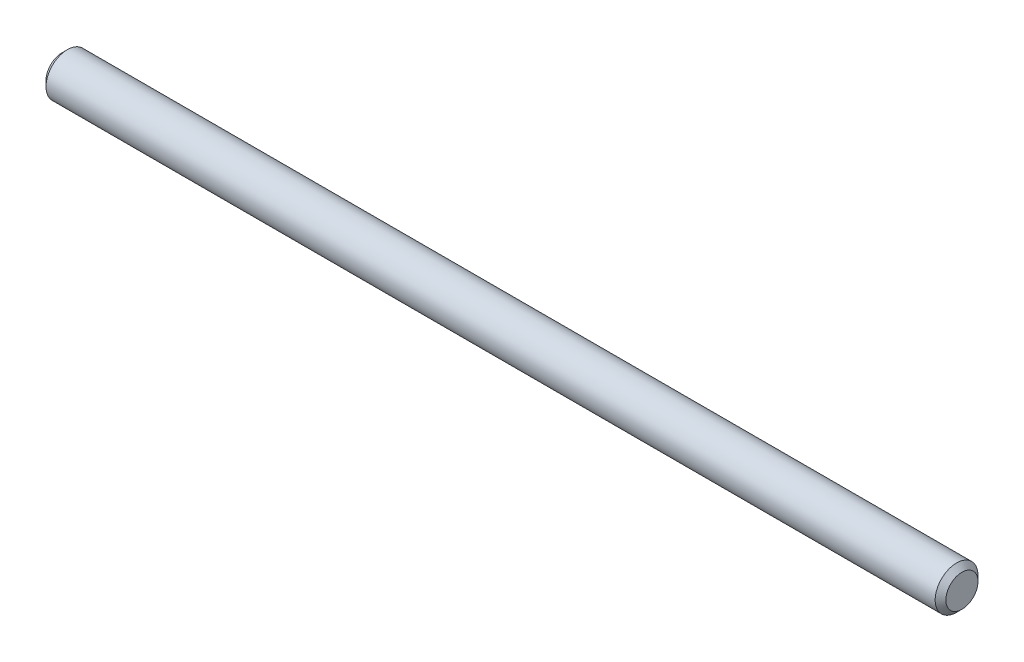
SolidWorks part; units mm, degrees
ref_plane "Front Plane" through (0, 0, 0) normal (0, 0, 1) x (1, 0, 0)
ref_plane "Top Plane" through (0, 0, 0) normal (0, 1, 0) x (1, 0, 0)
ref_plane "Right Plane" through (0, 0, 0) normal (1, 0, 0) x (0, 0, -1)
sketch "Sketch1" plane through (0, 0, 0) normal (1, 0, 0) x (0, 0, -1)
  circle A0 centre (0, 0) radius 2
  dimension "D1" = 4
extrude "Boss-Extrude1" add sketch "Sketch1" along normal blind 84
cosmetic thread "Cosmetic Thread1" parameters "D1"=8, "D2"=3.22
cosmetic thread "Cosmetic Thread2" parameters "D1"=8, "D2"=3.22
chamfer "Chamfer1" distance 0.5 angle 45 2 edges at (84, 0, -2) (0, 0, -2)
